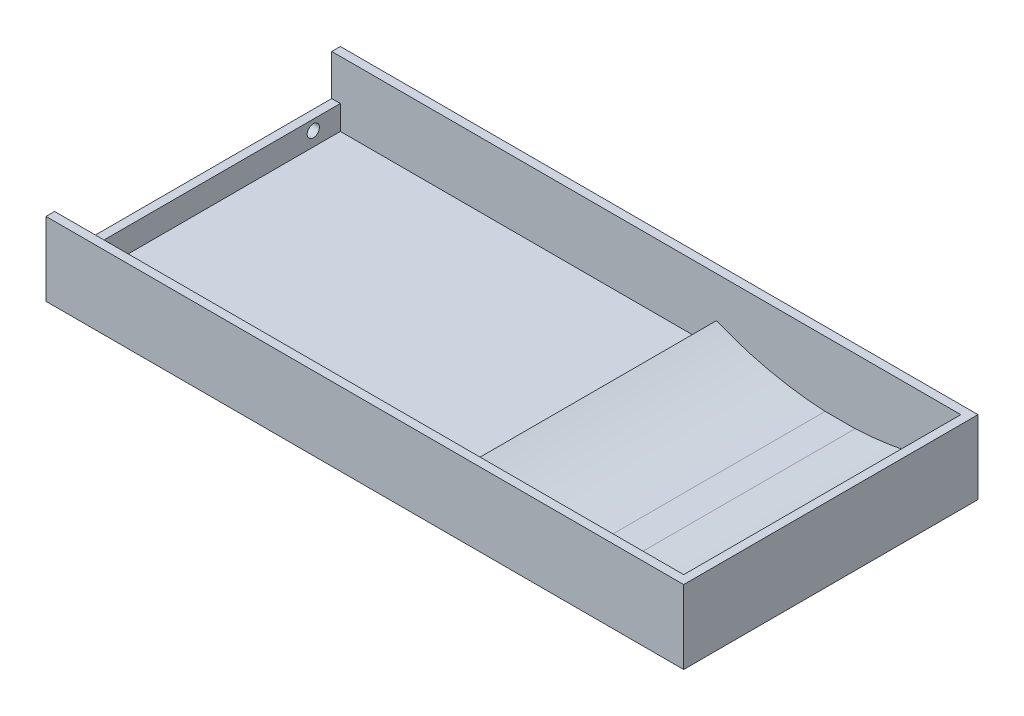
SolidWorks part; units mm, degrees
ref_plane "Alzado" through (0, 0, 0) normal (0, 0, 1) x (1, 0, 0)
ref_plane "Planta" through (0, 0, 0) normal (0, 1, 0) x (1, 0, 0)
ref_plane "Vista lateral" through (0, 0, 0) normal (1, 0, 0) x (0, 0, -1)
sketch "Croquis1" plane through (0, 0, 0) normal (0, 1, 0) x (1, 0, 0)
  line L1 (130, -60) -> (-130, -60)
  line L2 (130, -60) -> (130, 60)
  line L3 (130, 60) -> (-130, 60)
  line L4 (-130, -60) -> (-130, 60)
  line L5 (130, -60) -> (-130, 60) construction
  line L6 (130, 60) -> (-130, -60) construction
  point P0 (0, 0)
  dimension "D1" = 120
  dimension "D2" = 260
extrude "Saliente-Extruir1" add sketch "Croquis1" along normal blind 30
shell "Vaciado1" thickness 3.5 removed face at (0, 30, 0)
sketch "Croquis2" plane through (0, 0, -56.5) normal (0, 0, 1) x (1, 0, 0)
  line L1 (127.7593, 3.3589) -> (26.8536, 3.3589)
  line L2 (127.7593, 3.3589) -> (127.7593, 13.3589)
  line L4 (26.8536, 3.3589) -> (26.8536, 13.3589)
  arc A0 (26.8536, 13.3589) -> (127.7593, 13.3589) centre (77.3064, 135.6334) ccw
  line M2 (-126.5, 3.5) -> (126.5, 3.5)
  line M3 (126.5, 3.5) -> (126.5, 30)
  dimension "D1" = 10
extrude "Saliente-Extruir2" add sketch "Croquis2" along normal through all contours A0 L4 M2 | A0 L1 M3 | A0 M2 M3 region at (50.0659, 3.4282, -56.5) region at (38.9291, 6.4582, -56.5) region at (114.7412, 6.3064, -56.5)
sketch "Croquis3" plane through (-130, 0, 0) normal (-1, 0, 0) x (0, 0, 1)
  line L0 (56.5, 13.3589) -> (-56.5, 13.3589) construction
  line L1 (56.5, 13.3589) -> (-56.5, 13.3589) construction
  line L3 (-56.5, 13.3589) -> (56.5, 13.3589)
  line L4 (-56.5, 13.3589) -> (-56.5, 37.6168)
  line L5 (-56.5, 37.6168) -> (56.5, 37.6168)
  line L6 (56.5, 13.3589) -> (56.5, 37.6168)
extrude "Cortar-Extruir1" cut sketch "Croquis3" against normal blind 50.8
sketch "Croquis4" plane through (-130, 0, 0) normal (-1, 0, 0) x (0, 0, 1)
  circle A0 centre (-45.4839, 9.2415) radius 2.5037
  circle A1 centre (38.9743, 9.2415) radius 2.3368
extrude "Cortar-Extruir2" cut sketch "Croquis4" against normal blind 50.8
